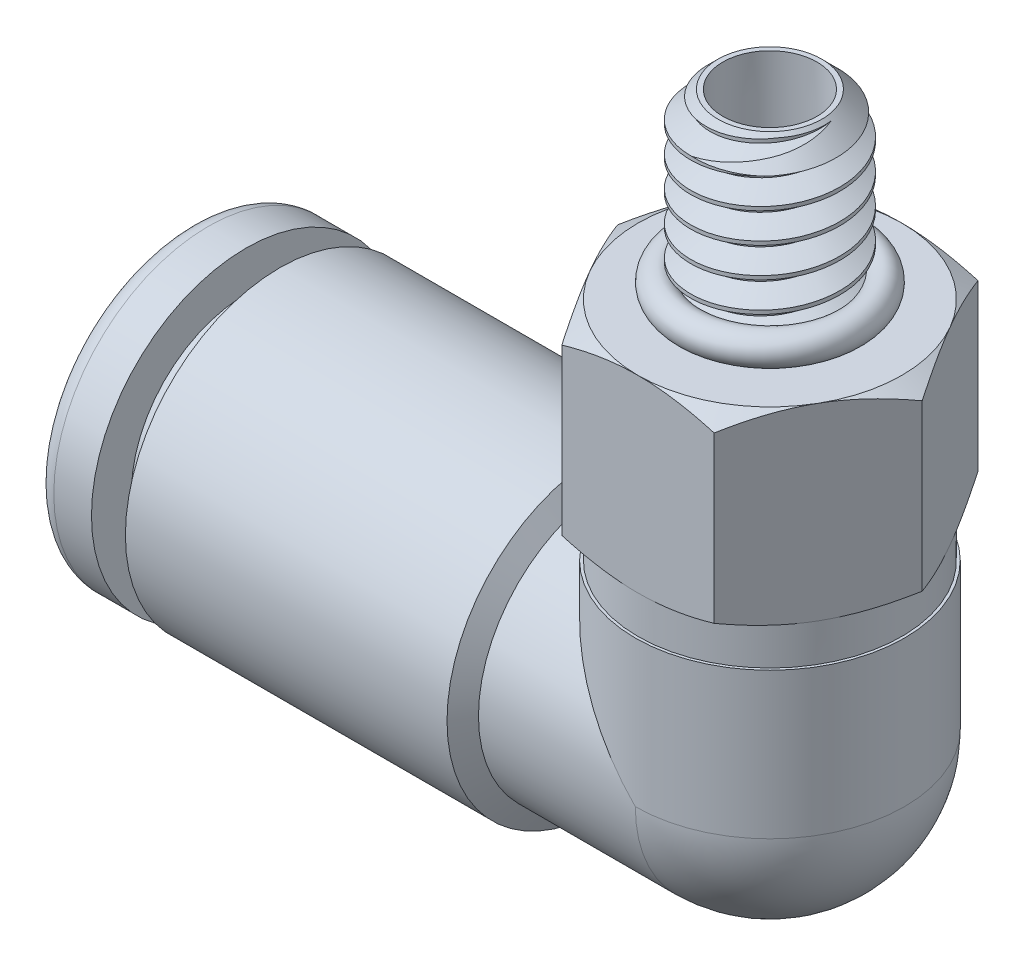
SolidWorks part; units mm, degrees
ref_plane "Front Plane" through (0, 0, 0) normal (0, 0, 1) x (1, 0, 0)
ref_plane "Top Plane" through (0, 0, 0) normal (0, 1, 0) x (1, 0, 0)
ref_plane "Right Plane" through (0, 0, 0) normal (1, 0, 0) x (0, 0, -1)
sketch "Sketch0" plane through (0, 0, 0) normal (0, 0, -1) x (-1, 0, 0)
  line L0 (0, 0) -> (-15.4, 0) construction
  line L1 (0, 4.1) -> (0, -4.1) construction
  line L2 (-13.3, 1.9844) -> (-13.3, -1.9844) construction
  line L3 (-13.4188, 9.874) -> (-17.3812, 9.874) construction
  line L4 (-18.9, 7.35) -> (-11.9, 7.35) construction
  line L5 (-15.4, 1.25) -> (-15.4, -1.25) construction
  line L6 (-15.4, 0) -> (-15.4, 14.7) construction
  line L7 (-11.9, 14.7) -> (-18.9, 14.7) construction
  point P3 (-13.3, 0)
  point P4 (-15.4, 11.2)
  point P11 (-15.4, 7.35)
  point P16 (-15.4, 11.2)
  point P20 (-15.4, 9.874)
  dimension "D1" = 8.2
  dimension "L1" = 15.4
  dimension "M" = 13.3
  dimension "A" = 15.3
  dimension "Tube OD" = 3.9688
  dimension "Thread OD" = 3.9624
  dimension "H" = 7
  dimension "D2" = 7
  dimension "ID" = 2.5
  dimension "Thread Length" = 4.826
  dimension "L2" = 14.7
sketch "Sketch1" plane through (0, 0, 0) normal (0, 0, -1) x (-1, 0, 0)
  line L0 (0, 3.6) -> (0, 2.4844)
  line L1 (-0.5, 4.1) -> (-1.5, 4.1)
  line L2 (-1.5, 4.1) -> (-1.5, 3.0422)
  line L3 (-1.5, 3.0422) -> (-2.4, 3.0422)
  line L4 (-2.4, 3.0422) -> (-2.4, 4.1)
  line L5 (-2.4, 4.1) -> (-10.9329, 4.1)
  line L6 (-2.4, 3.5711) -> (-11.2382, 3.5711) construction
  line L7 (0, 0) -> (-15.4, 0) construction
  line L8 (-13.3, 0) -> (-18.9711, 0)
  line L9 (-13.3, 1.9844) -> (-13.3, 0)
  line L10 (0, 0) -> (-15.4, 0) construction
  line L11 (-13.3, 1.9844) -> (-0.5, 1.9844)
  line L12 (0, 4.1) -> (0, -4.1) construction
  line L13 (-15.4, 3.5711) -> (-15.4, 0) construction
  line L15 (-11.2382, 3.5711) -> (-15.4, 3.5711)
  line L16 (-13.3, 0) -> (-10.9329, 4.1) construction
  line L17 (-10.9329, 4.1) -> (-11.2382, 3.5711)
  arc A0 (0, 3.6) -> (-0.5, 4.1) centre (-0.5, 3.6) ccw
  arc A1 (-0.5, 1.9844) -> (0, 2.4844) centre (-0.5, 2.4844) ccw
  arc A2 (-15.4, 3.5711) -> (-18.9711, 0) centre (-15.4, 0) ccw
  point P15 (0, 4.1)
  point P19 (0, 4.1)
  point P25 (0, 1.9844)
  dimension "D4" = 30
  dimension "D5" = 2.1156
  dimension "R" = 0.5
  dimension "D1" = 1.5
  dimension "D3" = 1.0578
  dimension "D2" = 0.9
revolve "Revolve1" add sketch "Sketch1" angle 360 about L10
ref_plane "Plane1" through (0, 9.874, 0) normal (0, 1, 0) x (0, 0, -1)
sketch "Sketch2" plane through (0, 9.874, 0) normal (0, 1, 0) x (0, 0, -1)
  circle A0 centre (0, -15.4) radius 1.9812
extrude "Extrude1" add sketch "Sketch2" along normal up to vertex (4.826 mm away) separate body up to point (15.4, 14.7, 0)
sketch "Sketch3" plane through (0, 14.7, 0) normal (0, 1, 0) x (0, 0, -1)
  circle A1 centre (0, -15.4) radius 1.9812
  circle A2 centre (0, -15.4) radius 1.9812
  point P0 (0, -13.4188)
  dimension "D1" = 0
curve "Helix/Spiral1" pitch 0.7937 height 5.6197 turns 7.08 parameters "Height"=5.6197, "Pitch"=0.7937
sketch "Sketch4" plane through (0, 0, 0) normal (0, 0, -1) x (-1, 0, 0)
  line L0 (-13.3329, 15.4441) -> (-14.0203, 15.0473) construction
  line L1 (-14.0203, 15.0473) -> (-13.3329, 14.6504) construction
  line L2 (-13.3329, 14.6504) -> (-13.3329, 15.4441) construction
  line L3 (-13.4188, 15.3945) -> (-13.4188, 14.7) construction
  line L4 (-13.3329, 15.0473) -> (-13.4188, 15.0473) construction
  line L5 (-13.4188, 15.0473) -> (-13.9344, 15.0473) construction
  line L6 (-13.9344, 15.0473) -> (-14.0203, 15.0473) construction
  line L7 (-13.9344, 15.0969) -> (-13.9344, 14.9977)
  line L8 (-13.3329, 14.6504) -> (-13.4188, 15.3945)
  line L9 (-13.3329, 14.6504) -> (-13.9344, 14.9977)
  line L10 (-13.4188, 15.3945) -> (-13.9344, 15.0969)
  line L11 (-14.0203, 15.0473) -> (-17.3812, 15.0473) construction
  line L12 (-17.3812, 15.0473) -> (-17.3812, 14.2535) construction
  line L13 (-17.3812, 14.2535) -> (-17.3812, 13.4598) construction
  line L14 (-17.3812, 13.4598) -> (-17.3812, 12.666) construction
  line L15 (-17.3812, 12.666) -> (-17.3812, 11.8723) construction
  line L16 (-17.3812, 14.7) -> (-17.3812, 9.874) construction
  dimension "D1" = 0.7937
  dimension "D2" = 0.0992
sketch "Sketch5" plane through (0, 14.7, 0) normal (0, 1, 0) x (0, 0, -1)
  circle A0 centre (0, -15.4) radius 1.3797
extrude "Extrude2" cut sketch "Sketch5" against normal up to vertex (3.5 mm away) draft 45 flip side to cut up to point (15.4, 11.2, 0)
sweep "Cut-Sweep1" cut profiles "Sketch4" path "Helix/Spiral1" align with end faces yes
sketch "Sketch6" plane through (0, 9.874, 0) normal (0, -1, 0) x (0, 0, 1)
  circle A2 centre (0, -15.4) radius 1.9812
  circle A3 centre (0, -15.4) radius 1.9812
  dimension "D1" = 0
extrude "Extrude3" add sketch "Sketch6" against normal blind 3 draft 45
sketch "Sketch7" plane through (0, 0, 0) normal (0, 0, 1) x (1, 0, 0)
  line L0 (15.4, 9.874) -> (15.4, 0)
  line L1 (15.4, 0) -> (15.4, 14.7) construction
  line L2 (15.4, 0) -> (18.9711, 0)
  line L4 (18.9, 3.874) -> (18.9, 9.874)
  line L5 (18.9, 9.874) -> (15.4, 9.874)
  line L6 (18.9711, 3.874) -> (18.9711, 0)
  line L7 (18.9711, 3.874) -> (18.9, 3.874)
  point P2 (15.4, 3.874)
  dimension "D2" = 6
revolve "Revolve2" add sketch "Sketch7" angle 360 about L0
sketch "Sketch8" plane through (0, 9.874, 0) normal (0, 1, 0) x (1, 0, 0)
  line L1 (19.4415, 0) -> (17.4207, 3.5)
  line L2 (17.4207, 3.5) -> (13.3793, 3.5)
  line L3 (13.3793, 3.5) -> (11.3585, 0)
  line L4 (11.3585, 0) -> (13.3793, -3.5)
  line L5 (13.3793, -3.5) -> (17.4207, -3.5)
  line L6 (17.4207, -3.5) -> (19.4415, 0)
  circle A1 centre (15.4, 0) radius 3.5 construction
  circle A2 centre (15.4, 0) radius 3.5 construction
extrude "Extrude4" add sketch "Sketch8" against normal blind 5
sketch "Sketch9" plane through (0, 9.874, 0) normal (0, 1, 0) x (1, 0, 0)
  circle A0 centre (15.4, 0) radius 3.5 construction
  circle A1 centre (15.4, 0) radius 3.5
extrude "Extrude5" cut sketch "Sketch9" against normal up to vertex (5 mm away) draft 60 flip side to cut up to point (11.3586, 4.874, 0)
sketch "Sketch10" plane through (0, 4.874, 0) normal (0, -1, 0) x (1, 0, 0)
  circle A1 centre (15.4, 0) radius 3.5
  circle A2 centre (15.4, 0) radius 3.5
  dimension "D1" = 0
extrude "Extrude6" cut sketch "Sketch10" against normal up to vertex (4.6874 mm away) draft 60 flip side to cut up to point (11.3586, 9.5614, 0)
sketch "Sketch11" plane through (13.3, 0, 0) normal (-1, 0, 0) x (0, 0, 1)
  circle A0 centre (0, 0) radius 1.9844
extrude "Extrude7" cut sketch "Sketch11" along normal up to vertex (13.3 mm away) up to point (0, 0, 0)
sketch "Sketch13" plane through (0, 0, 0) normal (-1, 0, 0) x (0, 0, 1)
  circle A0 centre (0, 0) radius 1.25
extrude "Cut-Extrude1" cut sketch "Sketch13" against normal up to vertex (15.4 mm away) up to point (15.4, 0, 3.5711)
sketch "Sketch14" plane through (15.4, 0, 0) normal (-1, 0, 0) x (0, 0, 1)
  line L0 (-1.25, 0) -> (1.25, 0) construction
  line L1 (1.25, 0) -> (-1.25, 0)
  circle A1 centre (0, 0) radius 1.25
  arc A2 (-1.25, 0) -> (1.25, 0) centre (0, 0) ccw
  dimension "D1" = 0
revolve "Cut-Revolve1" cut sketch "Sketch14" angle 90 about L0
sketch "Sketch15" plane through (0, 0, 0) normal (0, -1, 0) x (1, 0, 0)
  circle A0 centre (15.4, 0) radius 1.25
  arc A1 (15.4, -1.25) -> (15.4, 1.25) centre (15.4, 0) ccw construction
extrude "Cut-Extrude2" cut sketch "Sketch15" against normal through all draft 0.001
sketch "Sketch16" plane through (0, 0, 0) normal (0, 0, 1) x (1, 0, 0)
  line L0 (0.5, -1.9844) -> (13.3, -1.9844) construction
  line L2 (0.5, -1.9844) -> (13.3, -1.9844)
  line L3 (13.3, 1.9844) -> (0.5, 1.9844) construction
  line L4 (13.3, -1.25) -> (15.4, -1.25) construction
  line L5 (16.65, 0) -> (16.6497, 14.7) construction
  line L6 (13.3, -1.25) -> (15.4, -1.25)
  line L7 (16.65, 0) -> (16.6497, 14.7)
  line L8 (14.1503, 14.7) -> (14.15, 1.25) construction
  line L9 (14.1503, 14.7) -> (14.15, 1.25)
  line L10 (13.3, 1.9844) -> (13.3, -1.9844) construction
  line L11 (13.3, 1.9844) -> (13.3, -1.9844)
  line L12 (13.3, 1.9844) -> (0.5, 1.9844)
  line L13 (13.3, 1.9844) -> (13.3, 0) construction
  arc A0 (0, 2.4844) -> (0.5, 1.9844) centre (0.5, 2.4844) ccw construction
  arc A1 (0.5, -1.9844) -> (0, -2.4844) centre (0.5, -2.4844) ccw construction
  arc A2 (0, 2.4844) -> (0.5, 1.9844) centre (0.5, 2.4844) ccw
  arc A3 (0.5, -1.9844) -> (0, -2.4844) centre (0.5, -2.4844) ccw
  arc A4 (15.4, -1.25) -> (16.65, 0) centre (15.4, 0) ccw construction
  arc A5 (15.4, -1.25) -> (16.65, 0) centre (15.4, 0) ccw
sketch "Sketch17" plane through (0, 0, 0) normal (0, 0, 1) x (1, 0, 0)
  line L0 (15.4, 14.7) -> (15.4, 8.7441) construction
  line L1 (16.6497, 14.7) -> (14.1503, 14.7) construction
  line L2 (15.4, 9.874) -> (12.3689, 9.874) construction
  line L3 (13.6766, 15.0473) -> (13.6766, 13.4752) construction
  line L4 (13.4188, 15.0473) -> (13.9344, 15.0473) construction
  circle A0 centre (13.2766, 10.274) radius 0.4
  dimension "D1" = 0.8
revolve "Revolve4" add sketch "Sketch17" angle 360 about L0
equation "\"Height@Helix/Spiral1\" = \"Pitch@Helix/Spiral1\" + \"Thread Length@Sketch0\""
equation "\"D1@Sketch4\" = \"Pitch@Helix/Spiral1\""
equation "\"D2@Sketch4\" = \"D1@Sketch4\" * 1 / 8"
equation "\"D2@Sketch7\" = \"D1@Extrude4\"+1"
equation "\"D3@Sketch1\" = \"D5@Sketch1\"/2"
